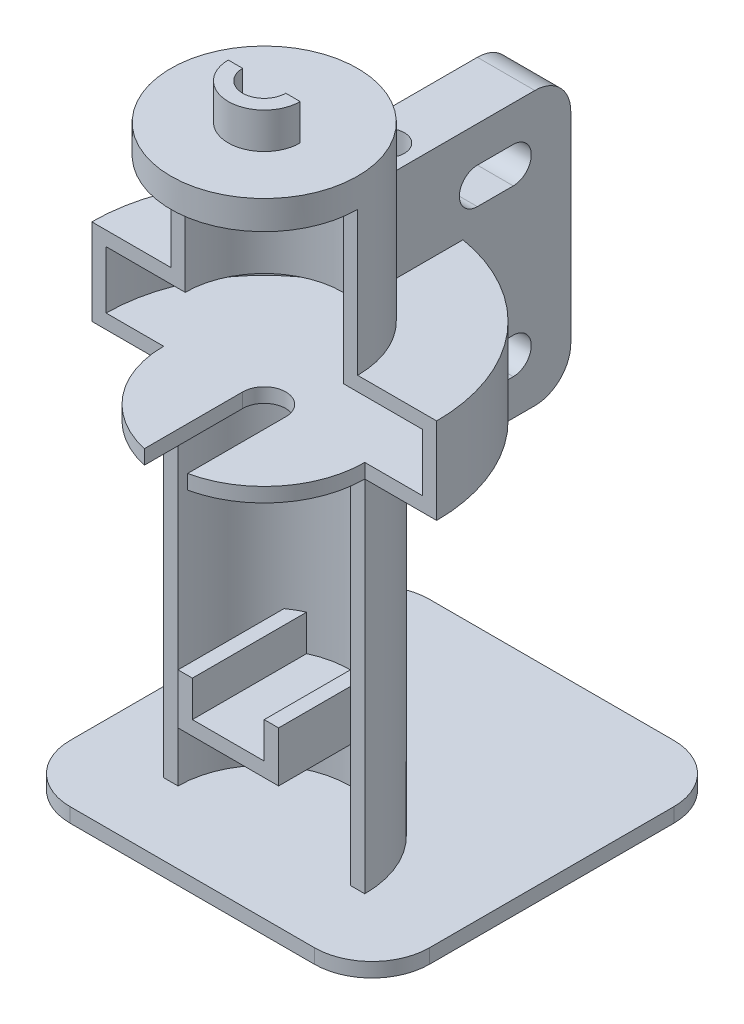
SolidWorks part; units mm, degrees
ref_plane "Front Plane" through (0, 0, 0) normal (0, 0, 1) x (1, 0, 0)
ref_plane "Top Plane" through (0, 0, 0) normal (0, 1, 0) x (1, 0, 0)
ref_plane "Right Plane" through (0, 0, 0) normal (1, 0, 0) x (0, 0, -1)
sketch "Sketch1" plane through (0, 0, 0) normal (0, 1, 0) x (1, 0, 0)
  line L0 (3, 0) -> (3, -13.6748)
  line L1 (-3, 0) -> (-3, -13.6748)
  line L2 (-14, 0) -> (-24, 0)
  line L3 (14, 0) -> (24, 0)
  circle A0 centre (0, 0) radius 14
  circle A1 centre (0, 0) radius 3
  arc A2 (24, 0) -> (-24, 0) centre (0, 0) ccw
  arc A3 (14, 0) -> (-14, 0) centre (0, 0) ccw
  dimension "D1" = 28
  dimension "D2" = 6
  dimension "D3" = 10
extrude "Motor-frontplate" add sketch "Sketch1" along normal blind 2 contours A1 L0 A0 L1 | L3 A2 L2 A3 region at (0, 0, -3.3937)
sketch "Sketch2" plane through (0, 0, 0) normal (0, -1, 0) x (1, 0, 0)
  line L2 (-12, 0) -> (-14, 0)
  line L3 (12, 0) -> (14, 0)
  arc A1 (-14, 0) -> (14, 0) centre (0, 0) ccw
  arc A3 (14, 0) -> (3, 13.6748) centre (0, 0) ccw construction
  arc A4 (-12, 0) -> (12, 0) centre (0, 0) ccw
  dimension "D1" = 2
extrude "Motorkrybbe" add sketch "Sketch2" along normal blind 50 contours A4 L3 A1 L2
sketch "Sketch5" plane through (0, 2, 0) normal (0, 1, 0) x (1, 0, 0)
  line L0 (-24, 0) -> (-22, 0)
  line L1 (24, 0) -> (22, 0)
  arc A1 (24, 0) -> (-24, 0) centre (0, 0) ccw construction
  arc A2 (22, 0) -> (-22, 0) centre (0, 0) ccw
  arc A3 (22, 0) -> (-22, 0) centre (0, 0) ccw
  arc A4 (24, 0) -> (-24, 0) centre (0, 0) ccw
  dimension "D1" = 2
extrude "Skygge - Kappe" add sketch "Sketch5" along normal blind 8 contours A3 L0 A4 L1
sketch "Sketch6" plane through (0, 10, 0) normal (0, 1, 0) x (1, 0, 0)
  line L0 (-24, 0) -> (-11, 0)
  line L1 (11, 0) -> (24, 0)
  arc A0 (-11, 0) -> (11, 0) centre (0, 0) cw
  arc A1 (24, 0) -> (-24, 0) centre (0, 0) ccw construction
  arc A2 (24, 0) -> (-24, 0) centre (0, 0) ccw
  dimension "D1" = 11
extrude "Skygge - Topp" add sketch "Sketch6" along normal blind 2
sketch "Sketch7" plane through (0, 12, 0) normal (0, 1, 0) x (1, 0, 0)
  line L0 (-4, 12.3693) -> (-4, 23.6643)
  line L1 (4, 23.6643) -> (4, 12.3693)
  arc A0 (24, 0) -> (-24, 0) centre (0, 0) ccw construction
  arc A1 (11, 0) -> (-11, 0) centre (0, 0) ccw construction
  arc A2 (24, 0) -> (-24, 0) centre (0, 0) ccw
  arc A3 (11, 0) -> (-11, 0) centre (0, 0) ccw
  arc A4 (4, 12.3693) -> (-4, 12.3693) centre (0, 0) ccw
  arc A5 (4, 23.6643) -> (-4, 23.6643) centre (0, 0) ccw
  dimension "D3" = 2
  dimension "D1" = 4
  dimension "D2" = 4
extrude "LEDholder - Topp" add sketch "Sketch7" along normal blind 13 contours L1 A4 L0 A5
sketch "Sketch8" plane through (0, 0, 0) normal (0, -1, 0) x (1, 0, 0)
  line L0 (4, -23.6643) -> (4, -13.4164)
  line L1 (4, -23.6643) -> (4, -12.3693) construction
  line L2 (-4, -23.6643) -> (-4, -13.4164)
  line L3 (-4, -12.3693) -> (-4, -23.6643) construction
  arc A0 (-14, 0) -> (14, 0) centre (0, 0) ccw construction
  arc A1 (4, -13.4164) -> (-4.105, -13.3846) centre (0, 0) cw
  arc A2 (4, -23.6643) -> (-4, -23.6643) centre (0, 0) cw
  arc M1 (14, 0) -> (-14, 0) centre (0, 0) cw
  arc M3 (-24, 0) -> (24, 0) centre (0, 0) ccw
extrude "LEDholder - Bunn" add sketch "Sketch8" along normal blind 13 contours L2 L0 M3 M1 region at (0, 0, -18.8468)
sketch "Sketch10" plane through (0, -13, 0) normal (0, -1, 0) x (1, 0, 0)
  line L2 (0, 0) -> (0, -14)
  line L3 (0, -14) -> (0, -14.5)
  line L4 (0, -14.5) -> (0, -17)
  arc A0 (-4, -13.4164) -> (4, -13.4164) centre (0, 0) ccw construction
  arc A1 (-4, -13.4164) -> (4, -13.4164) centre (0, 0) ccw
  circle A3 centre (0, -17) radius 2.5
  dimension "D1" = 5
  dimension "D2" = 0.5
extrude "LEDhull" cut sketch "Sketch10" against normal through all contours A3 region at (-1.7178, -13, -18.7178)
sketch "Sketch11" plane through (0, 12, 0) normal (0, 1, 0) x (1, 0, 0)
  line L0 (-24, 0) -> (-11, 0) construction
  line L1 (11, 0) -> (24, 0) construction
  line L2 (-13, 0) -> (-11, 0)
  line L3 (13, 0) -> (11, 0)
  arc A0 (-11, 0) -> (11, 0) centre (0, 0) cw
  arc A1 (11, 0) -> (-11, 0) centre (0, 0) ccw construction
  arc A2 (-13, 0) -> (13, 0) centre (0, 0) cw
  dimension "D1" = 2
extrude "Rotorkappe - Vegg" add sketch "Sketch11" along normal blind 20
sketch "Sketch12" plane through (0, 32, 0) normal (0, 1, 0) x (1, 0, 0)
  circle A0 centre (0, 0) radius 13
extrude "Laserholder" add sketch "Sketch12" along normal blind 4
hole_wizard "Laser - hull" positions "Sketch13" profile "Sketch15" hole size "Ø6.0" standard "ISO" end condition up to next
sketch "Sketch13" plane through (0, 36, 0) normal (0, 1, 0) x (1, 0, 0)
  point P0 (0, 0)
sketch "Sketch15" plane through (0, 36, 0) normal (1, 0, 0) x (0, 0, 1)
  line L0 (0, 0) -> (0, 4)
  line L1 (0, 4) -> (3, 4)
  line L2 (3, 4) -> (3, 0)
  line L5 (3, 0) -> (0, 0)
  line L11 (0, -6.35) -> (0, 107.95) construction
  dimension "Thru Hole Dia." = 6
  dimension "Thru Hole Depth" = 4
sketch "Sketch16" plane through (0, -50, 0) normal (0, -1, 0) x (1, 0, 0)
  line L1 (-17, -40) -> (17, -40)
  line L2 (-25, -32) -> (-25, 2)
  line L3 (-17, 10) -> (17, 10)
  line L4 (25, -32) -> (25, 2)
  arc A0 (-25, 2) -> (-17, 10) centre (-17, 2) cw
  arc A1 (-17, -40) -> (-25, -32) centre (-17, -32) cw
  arc A2 (17, -40) -> (25, -32) centre (17, -32) ccw
  arc A3 (17, 10) -> (25, 2) centre (17, 2) cw
  point P0 (0, 0)
  dimension "D3" = 8
  dimension "D1" = 10
  dimension "D2" = 25
  dimension "D4" = 50
  dimension "D5" = 50
extrude "Bunnplate" add sketch "Sketch16" along normal blind 2
sketch "Sketch19" plane through (0, 0, 0) normal (0, 0, 1) x (1, 0, 0)
  line L0 (0, -36) -> (-5, -36)
  line L9 (-5, -36) -> (-5, -31)
  line L10 (-5, -31) -> (-7, -31)
  line L11 (-7, -31) -> (-7, -38)
  line L12 (-7, -38) -> (0, -38)
  line L13 (0, -38) -> (0, -36)
  line L14 (0, 0) -> (0, -36) construction
  dimension "D1" = 31
  dimension "D2" = 2
  dimension "D3" = 5
  dimension "D4" = 2
  dimension "D5" = 5
extrude "Boss-Extrude12" add sketch "Sketch19" along normal blind 5 and the other way up to next
mirror "Mirror2" about plane through (0, -38, -40.002) normal (1, 0, 0) of "Boss-Extrude12"
sketch "Sketch20" plane through (0, 25, 0) normal (0, 1, 0) x (1, 0, 0)
  line L0 (4, 23.6643) -> (4, 38.6643)
  line L1 (4, 38.6643) -> (-4, 38.6643)
  line L2 (-4, 38.6643) -> (-4, 23.6643)
  arc A0 (4, 23.6643) -> (-4, 23.6643) centre (0, 0) ccw construction
  arc A1 (4, 23.6643) -> (-4, 23.6643) centre (0, 0) ccw
  dimension "D1" = 15
extrude "LED - kabelholder" add sketch "Sketch20" against normal blind 38
sketch "Sketch21" plane through (4, 0, 0) normal (1, 0, 0) x (0, 0, -1)
  line L0 (25.6643, 17.5) -> (30.6643, 17.5) construction
  line L1 (25.6643, 20) -> (30.6643, 20)
  line L2 (25.6643, 15) -> (30.6643, 15)
  line L3 (38.6643, -13) -> (38.6643, 25) construction
  line L4 (12.3693, 25) -> (38.6643, -13) construction
  line L5 (38.6643, 25) -> (12.3693, 25) construction
  line L6 (25.5168, 6) -> (38.6643, 6)
  line L7 (25.6643, -5.5) -> (30.6643, -5.5) construction
  line L8 (25.6643, -8) -> (30.6643, -8)
  line L9 (25.6643, -3) -> (30.6643, -3)
  arc A0 (25.6643, 20) -> (25.6643, 15) centre (25.6643, 17.5) ccw
  arc A1 (30.6643, 15) -> (30.6643, 20) centre (30.6643, 17.5) ccw
  arc A2 (25.6643, -8) -> (25.6643, -3) centre (25.6643, -5.5) cw
  arc A3 (30.6643, -3) -> (30.6643, -8) centre (30.6643, -5.5) cw
  point P2 (28.1643, 17.5)
  point P19 (28.1643, -5.5)
  dimension "D1" = 8
  dimension "D2" = 5
  dimension "D3" = 5
  dimension "D4" = 5
extrude "Kabelholder - hull" cut sketch "Sketch21" against normal up to next contours L2 A1 L1 A0 | A3 L9 A2 L8 region at (4, 17.5, -28.1643) region at (4, -5.5, -28.1643)
fillet "Fillet1" radius 5 2 edges at (0, -13, -38.6643) (0, 25, -38.6643)
sketch "Sketch22" plane through (0, 36, 0) normal (0, 1, 0) x (1, 0, 0)
  line L0 (-3, 0) -> (-5, 0)
  line L1 (3, 0) -> (5, 0)
  circle A1 centre (0, 0) radius 3 construction
  arc A2 (3, 0) -> (-3, 0) centre (0, 0) cw
  arc A3 (5, 0) -> (-5, 0) centre (0, 0) cw
  dimension "D1" = 2
extrude "Boss-Extrude14" add sketch "Sketch22" along normal blind 5
